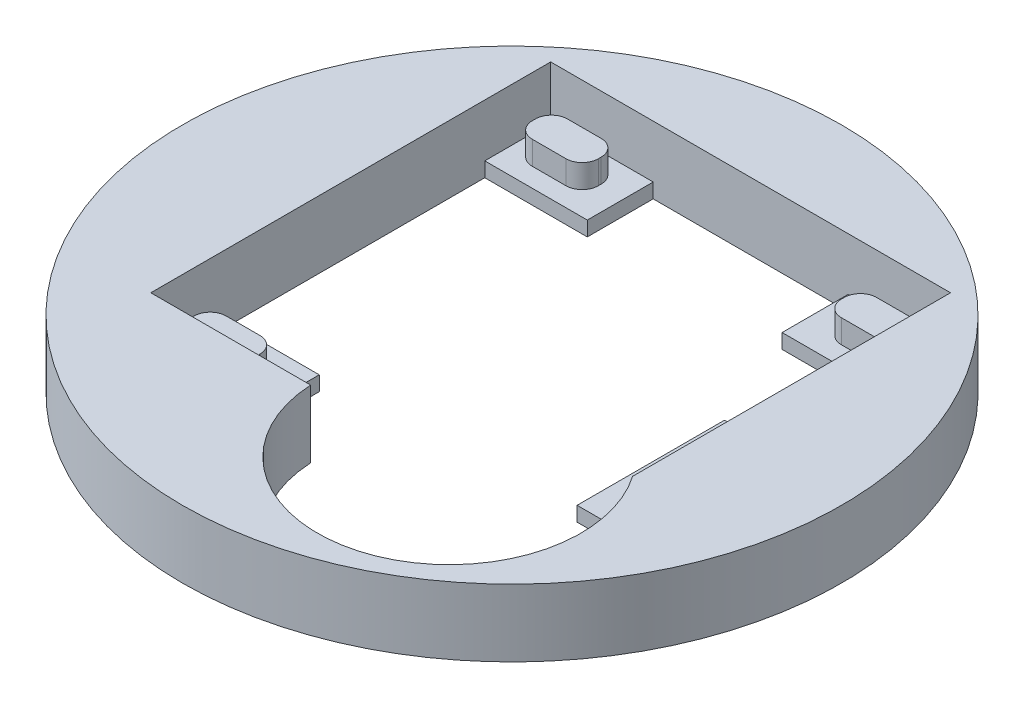
SolidWorks part; units mm, degrees
ref_plane "Front Plane" through (0, 0, 0) normal (0, 0, 1) x (1, 0, 0)
ref_plane "Top Plane" through (0, 0, 0) normal (0, 1, 0) x (1, 0, 0)
ref_plane "Right Plane" through (0, 0, 0) normal (1, 0, 0) x (0, 0, -1)
sketch "Sketch1" plane through (0, 0, 0) normal (0, 1, 0) x (1, 0, 0)
  line L6 (0, 2.6405) -> (0, 6.4014) construction
  line L7 (-13.65, 16.2905) -> (-6.65, 16.2905)
  line L8 (-13.65, 16.2905) -> (-13.65, 11.7905)
  line L9 (-13.65, 11.7905) -> (-6.65, 11.7905)
  line L10 (-6.65, 16.2905) -> (-6.65, 11.7905)
  line L11 (13.65, 11.7905) -> (6.65, 11.7905)
  line L12 (6.65, 16.2905) -> (6.65, 11.7905)
  line L13 (0, 2.6405) -> (-4.2539, 2.6405) construction
  line L14 (-6.65, -11.0095) -> (-6.65, -6.5095)
  line L15 (-13.65, -6.5095) -> (-6.65, -6.5095)
  line L16 (13.6557, -5.4225) -> (9.8672, -5.4225)
  line L17 (9.8672, -5.4225) -> (9.8672, 4.6425)
  line L18 (9.8672, 4.6425) -> (13.65, 4.6425)
  line L19 (-13.65, -11.0095) -> (13.65, -11.0095)
  line L20 (6.25, -19.5367) -> (6.25, -17.8592)
  line L21 (-13.65, -11.0095) -> (-13.65, 16.2905)
  line L22 (-13.65, 16.2905) -> (13.65, 16.2905)
  line L23 (13.65, -11.0095) -> (13.65, 16.2905)
  line L24 (-13.65, -11.0095) -> (13.65, 16.2905) construction
  line L25 (-13.65, 16.2905) -> (13.65, -11.0095) construction
  arc A7 (-2.7376, -11.0095) -> (13.65, -5.4142) centre (6.25, -10.5367) ccw
  circle A8 centre (0, 0) radius 22.5
  point P1 (0, 2.6405)
  point P39 (13.3874, -7.0367)
  dimension "D4" = 27.3
  dimension "D5" = 18
  dimension "D1" = 7
  dimension "D2" = 4.5
  dimension "D3" = 27.3
extrude "Boss-Extrude1" add sketch "Sketch1" along normal blind 3.6 contours A8 L23 L19 L21 L22 region at (-21.8636, 0, 0)
extrude "Boss-Extrude2" add sketch "Sketch1<3>" against normal blind 1 contours A8 L23 L19 L21 L8 L7 L22 | L10 L7 L8 L9 | L21 L19 L14 L15 | L11 L23 L22 L12 | L23 L18 L17 region at (-10.15, 0, -14.0405) region at (10.15, 0, -14.0405) region at (-10.15, 0, 8.7595) region at (11.7586, 0, 0.39) region at (-21.8636, 0, 0)
sketch "Sketch1<3>" plane through (0, 0, 0) normal (0, 1, 0) x (1, 0, 0) same geometry as "Sketch1"
sketch "Sketch2" plane through (0, 0, 0) normal (0, 1, 0) x (1, 0, 0)
  line L0 (-13.65, -11.0095) -> (-13.65, 16.2905) construction
  line L1 (-11.7, 13.0905) -> (-9.4, 13.0905)
  line L2 (-12.8, 14.1905) -> (-12.8, 14.3905)
  line L3 (-11.7, 15.4905) -> (-9.4, 15.4905)
  line L4 (-8.3, 14.1905) -> (-8.3, 14.3905)
  line L5 (-12.8, 13.0905) -> (-8.3, 15.4905) construction
  line L6 (-12.8, 15.4905) -> (-8.3, 13.0905) construction
  line L7 (-13.65, 16.2905) -> (13.65, 16.2905) construction
  line L8 (0, 0) -> (0, 3.7793) construction
  line L9 (0, 0) -> (4.0896, 0) construction
  line L10 (-13.65, 2.6405) -> (-7.6863, 2.6405) construction
  line L11 (0, 16.2905) -> (0, 12.7964) construction
  line L12 (-11.7, -10.2095) -> (-9.4, -10.2095)
  line L13 (-8.3, -8.9095) -> (-8.3, -9.1095)
  line L14 (-11.7, -7.8095) -> (-9.4, -7.8095)
  line L15 (-12.8, -8.9095) -> (-12.8, -9.1095)
  line L16 (11.7, 15.4905) -> (9.4, 15.4905)
  line L17 (8.3, 14.1905) -> (8.3, 14.3905)
  line L18 (11.7, 13.0905) -> (9.4, 13.0905)
  line L19 (12.8, 14.1905) -> (12.8, 14.3905)
  arc A0 (-12.8, 14.3905) -> (-11.7, 15.4905) centre (-11.7, 14.3905) cw
  arc A1 (-12.8, 14.1905) -> (-11.7, 13.0905) centre (-11.7, 14.1905) ccw
  arc A2 (-9.4, 13.0905) -> (-8.3, 14.1905) centre (-9.4, 14.1905) ccw
  arc A3 (-8.3, 14.3905) -> (-9.4, 15.4905) centre (-9.4, 14.3905) ccw
  arc A4 (-8.3, -9.1095) -> (-9.4, -10.2095) centre (-9.4, -9.1095) cw
  arc A5 (-9.4, -7.8095) -> (-8.3, -8.9095) centre (-9.4, -8.9095) cw
  arc A6 (-12.8, -9.1095) -> (-11.7, -10.2095) centre (-11.7, -9.1095) ccw
  arc A7 (-12.8, -8.9095) -> (-11.7, -7.8095) centre (-11.7, -8.9095) cw
  arc A8 (8.3, 14.3905) -> (9.4, 15.4905) centre (9.4, 14.3905) cw
  arc A9 (9.4, 13.0905) -> (8.3, 14.1905) centre (9.4, 14.1905) cw
  arc A10 (12.8, 14.3905) -> (11.7, 15.4905) centre (11.7, 14.3905) ccw
  arc A11 (12.8, 14.1905) -> (11.7, 13.0905) centre (11.7, 14.1905) cw
  point P0 (-10.55, 14.2905)
  dimension "D5" = 1.1
  dimension "D1" = 4.5
  dimension "D2" = 2.4
  dimension "D3" = 0.85
  dimension "D4" = 0.8
extrude "Boss-Extrude3" add sketch "Sketch2" along normal blind 1.6
